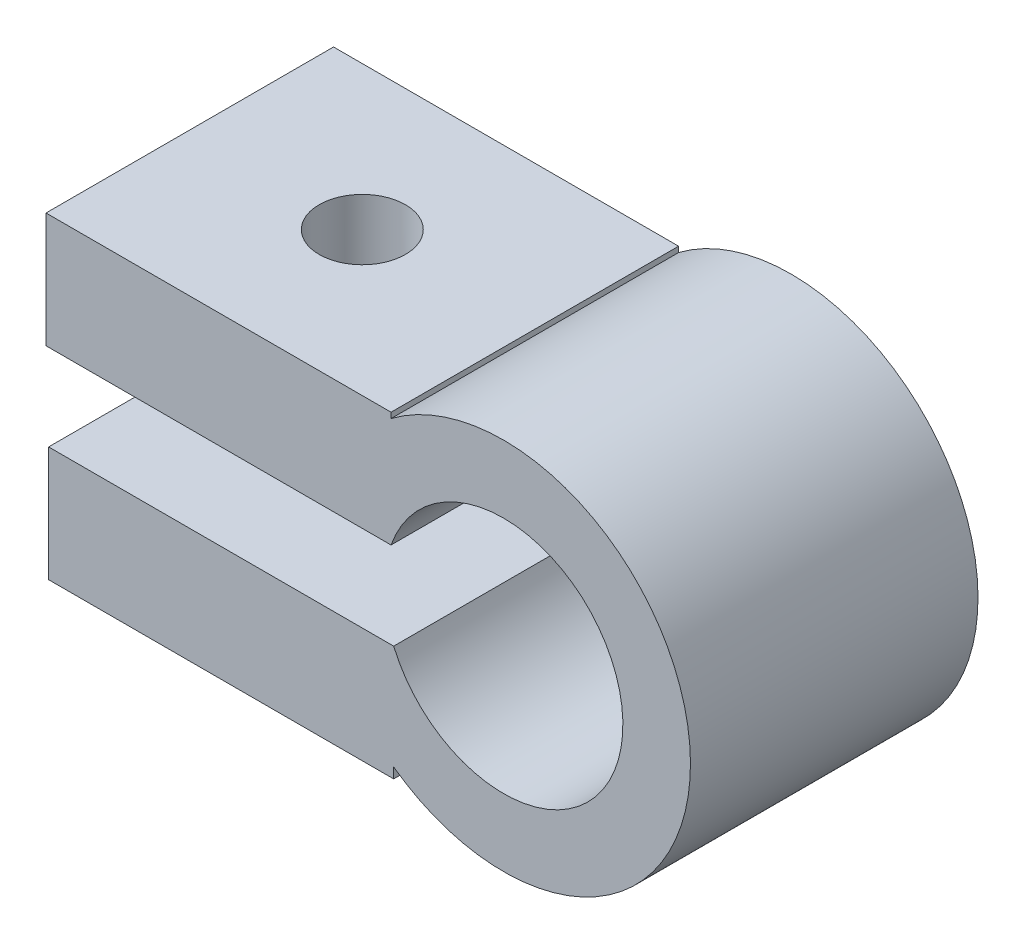
SolidWorks part; units mm, degrees
ref_plane "Front Plane" through (0, 0, 0) normal (0, 0, 1) x (1, 0, 0)
ref_plane "Top Plane" through (0, 0, 0) normal (0, 1, 0) x (1, 0, 0)
ref_plane "Right Plane" through (0, 0, 0) normal (1, 0, 0) x (0, 0, -1)
sketch "Sketch1" plane through (0, 0, 0) normal (0, 0, 1) x (1, 0, 0)
  circle A0 centre (-12.3154, 2.5507) radius 4.15
  circle A1 centre (-12.3154, 2.5507) radius 6.5
  dimension "D1" = 8.3
  dimension "D2" = 13
extrude "Boss-Extrude1" add sketch "Sketch1" along normal blind 10
sketch "Sketch2" plane through (0, 0, 10) normal (0, 0, 1) x (1, 0, 0)
  line L1 (-18.9664, 3.9327) -> (-15.7482, 3.9327)
  line L2 (-18.9664, 3.9327) -> (-18.9664, 0.9327)
  line L3 (-18.9664, 0.9327) -> (-15.7482, 0.9327)
  line L4 (-15.7482, 3.9327) -> (-15.7482, 0.9327)
  dimension "D1" = 3
extrude "Cut-Extrude1" cut sketch "Sketch2" against normal blind 33
sketch "Sketch3" plane through (0, 0, 10) normal (0, 0, 1) x (1, 0, 0)
  line L0 (-16.137, 0.9327) -> (-28.137, 0.9327)
  line L1 (-16.2286, 7.9327) -> (-28.2286, 7.9327)
  line L2 (-16.2286, 7.9327) -> (-16.2286, 3.9327)
  line L3 (-16.2286, 3.9327) -> (-28.2286, 3.9327)
  line L4 (-28.2286, 7.9327) -> (-28.2286, 3.9327)
  line L5 (-16.137, 0.9327) -> (-16.137, -3.0673)
  line L6 (-16.137, -3.0673) -> (-28.137, -3.0673)
  line L7 (-28.137, 0.9327) -> (-28.137, -3.0673)
  line L8 (-16.2286, 3.9327) -> (-18.6668, 3.9327) construction
  line L9 (-18.6108, 0.9327) -> (-16.137, 0.9327) construction
  dimension "D1" = 12
  dimension "D2" = 0
  dimension "D3" = 0
  dimension "D4" = 0
  dimension "D5" = 0
  dimension "D6" = 12
  dimension "D7" = 4
  dimension "D8" = 4
extrude "Boss-Extrude2" add sketch "Sketch3" against normal blind 10 contours L2 L1 L4 L3 | L0 L7 L6 L5
sketch "Sketch4" plane through (0, 7.9327, 0) normal (0, 1, 0) x (1, 0, 0)
  line L0 (-16.2286, 0) -> (-28.2286, 0) construction
  line L1 (-28.2286, 0) -> (-28.2286, -10) construction
  circle A0 centre (-22.2286, -5) radius 1.5
  dimension "D1" = 5
  dimension "D2" = 6
  dimension "D3" = 3
extrude "Cut-Extrude2" cut sketch "Sketch4" against normal blind 40
sketch "Sketch5" plane through (0, -3.0673, 0) normal (0, -1, 0) x (-1, 0, 0)
  line L1 (19.0511, -6.6695) -> (22.0511, -8.4015)
  line L2 (22.0511, -8.4015) -> (25.0511, -6.6695)
  line L3 (25.0511, -6.6695) -> (25.0511, -3.2054)
  line L4 (25.0511, -3.2054) -> (22.0511, -1.4733)
  line L5 (22.0511, -1.4733) -> (19.0511, -3.2054)
  line L6 (19.0511, -3.2054) -> (19.0511, -6.6695)
  circle A0 centre (22.0511, -4.9374) radius 3 construction
  dimension "D1" = 6
extrude "Cut-Extrude3" cut sketch "Sketch5" against normal blind 3
